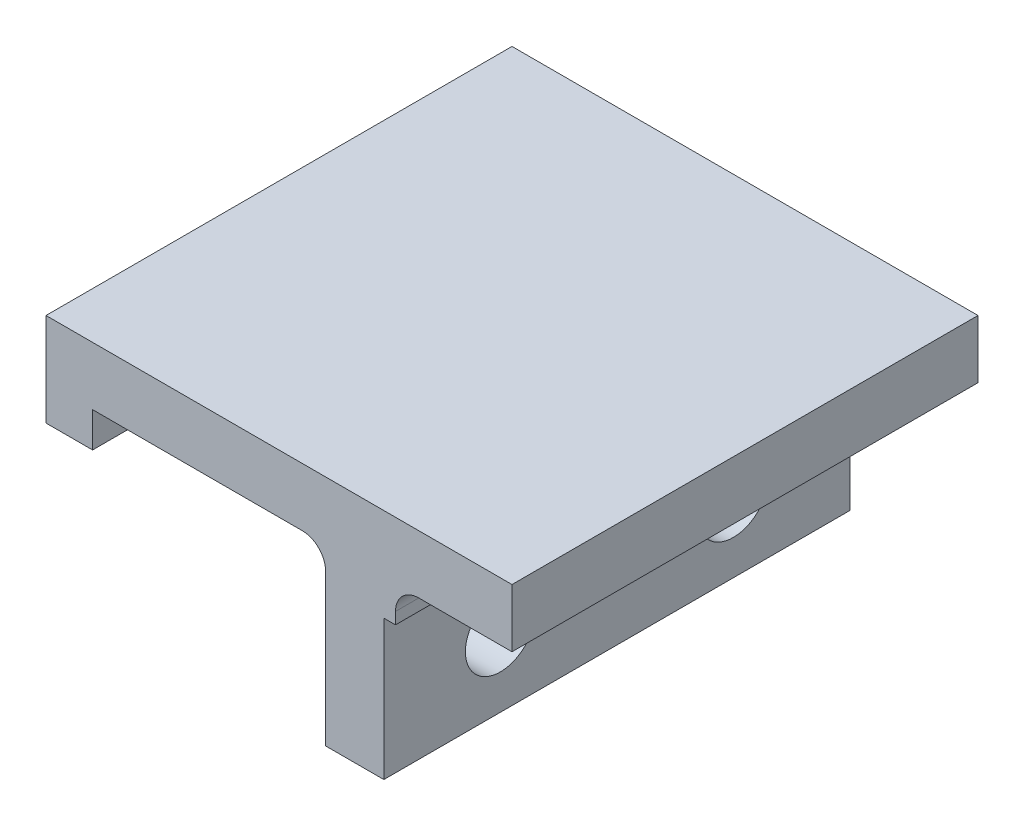
SolidWorks part; units mm, degrees
ref_plane "Front" through (0, 0, 0) normal (0, 0, 1) x (1, 0, 0)
ref_plane "Top" through (0, 0, 0) normal (0, 1, 0) x (1, 0, 0)
ref_plane "Right" through (0, 0, 0) normal (1, 0, 0) x (0, 0, -1)
sketch "Szkic1" plane through (0, 0, 0) normal (1, 0, 0) x (0, 0, -1)
  line L0 (-30, -6) -> (10, -6)
  line L1 (-30, 9) -> (10, 9)
  line L2 (10, 9) -> (10, -6)
  line L3 (-30, 9) -> (-30, -6)
  circle A0 centre (0, 0) radius 3
  circle A1 centre (-20, 0) radius 3
  dimension "D1" = 20
  dimension "D2" = 6
  dimension "D3" = 6
  dimension "D4" = 40
  dimension "D5" = 10
  dimension "D6" = 6
  dimension "D7" = 15
extrude "Dodanie-wyciągnięcie1" add sketch "Szkic1" along normal blind 6
sketch "Szkic2" plane through (0, 9, 0) normal (0, 1, 0) x (1, 0, 0)
  line L0 (-24, 10) -> (-24, -30)
  line L1 (-24, -30) -> (16, -30)
  line L2 (16, -30) -> (16, 10)
  line L3 (16, 10) -> (-24, 10)
  line L4 (6, 10) -> (0, 10) construction
  line L5 (6, -30) -> (0, -30) construction
  line L6 (6, 10) -> (6, -30) construction
  line L7 (0, 10) -> (0, -30) construction
  dimension "D1" = 0
  dimension "D2" = 0
  dimension "D3" = 10
  dimension "D4" = 24
extrude "Dodanie-wyciągnięcie2" add sketch "Szkic2" along normal blind 5
sketch "Szkic3" plane through (6, 0, 0) normal (1, 0, 0) x (0, 0, -1)
  line L0 (10, -6) -> (10, 9) construction
  line L1 (-30, -6) -> (10, -6)
  line L2 (-30, -6) -> (-30, 6)
  line L3 (-30, 6) -> (10, 6)
  line L4 (10, -6) -> (10, 6)
  dimension "D1" = 12
extrude "Wytnij-wyciągnięcie1" cut sketch "Szkic3" against normal blind 1
fillet "Zaokrąglenie1" radius 2 2 edges at (0, 9, 10) (6, 9, 10)
sketch "Szkic4" plane through (0, 9, 0) normal (0, -1, 0) x (1, 0, 0)
  line L0 (-2, -10) -> (-24, -10) construction
  line L1 (-24, 30) -> (-20, 30)
  line L2 (-24, 30) -> (-24, -10)
  line L3 (-24, -10) -> (-20, -10)
  line L4 (-20, 30) -> (-20, -10)
  dimension "D1" = 4
extrude "Dodanie-wyciągnięcie3" add sketch "Szkic4" along normal blind 3
